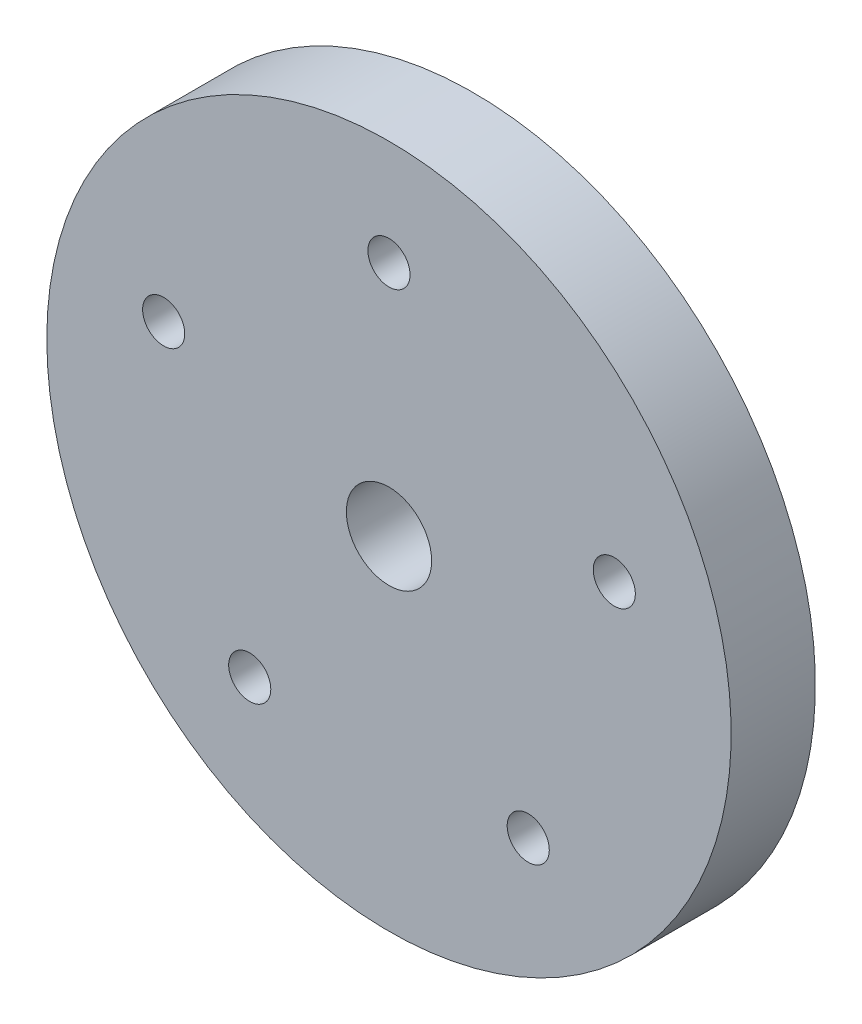
SolidWorks part; units mm, degrees
ref_plane "Ebene vorne" through (0, 0, 0) normal (0, 0, 1) x (1, 0, 0)
ref_plane "Ebene oben" through (0, 0, 0) normal (0, 1, 0) x (1, 0, 0)
ref_plane "Ebene rechts" through (0, 0, 0) normal (1, 0, 0) x (0, 0, -1)
sketch "Skizze1" plane through (0, 0, 0) normal (1, 0, 0) x (0, 0, -1)
  line L0 (0, 0) -> (0, -44862.1348) construction
  line L1 (0, 0) -> (-44862.1348, 0) construction
  line L2 (0, 0) -> (20, 0)
  line L3 (20, 0) -> (20, 15)
  line L4 (20, 15) -> (8, 15)
  line L5 (8, 15) -> (8, 32.5)
  line L6 (8, 32.5) -> (0, 32.5)
  line L7 (0, 32.5) -> (0, 0)
  dimension "D1" = 30
  dimension "D2" = 65
  dimension "D3" = 20
  dimension "D4" = 12
revolve "Rotation1" add sketch "Skizze1" angle 360 about L1
hole_wizard "Ø4.0 (4) Heat Insert M3" positions "Skizze2" profile "Skizze3" hole size "Ø4.0" standard "ISO" end condition through all
sketch "Skizze2" plane through (0, 0, 0) normal (0, 0, 1) x (1, 0, 0)
  circle A0 centre (0, 0) radius 22.5 construction
  point P7 (0, 22.5)
  dimension "D1" = 45
sketch "Skizze3" plane through (0, 22.5, 0) normal (1, 0, 0) x (0, -1, 0)
  line L0 (0, 0) -> (0, 20)
  line L1 (0, 20) -> (2, 20)
  line L2 (2, 20) -> (2, 0)
  line L5 (2, 0) -> (0, 0)
  line L11 (0, -6.35) -> (0, 107.95) construction
  dimension "Bohrerdurchmesser" = 4
  dimension "Bohrungstiefe" = 20
hole_wizard "Ø8.1 (8.1) Durchmesser Bohrung1" positions "Skizze4" profile "Skizze5" hole size "Ø8.1" standard "ISO" end condition through all
sketch "Skizze4" plane through (0, 0, 0) normal (0, 0, 1) x (1, 0, 0)
  point P0 (0, 0)
sketch "Skizze5" plane through (0, 0, 0) normal (1, 0, 0) x (0, -1, 0)
  line L0 (0, 0) -> (0, 20)
  line L1 (0, 20) -> (4.05, 20)
  line L2 (4.05, 20) -> (4.05, 0)
  line L5 (4.05, 0) -> (0, 0)
  line L11 (0, -6.35) -> (0, 107.95) construction
  dimension "Bohrerdurchmesser" = 8.1
  dimension "Bohrungstiefe" = 20
sketch "Skizze8" plane through (0, 0, -20) normal (0, 0, -1) x (-1, 0, 0)
  line L0 (0, 0) -> (0, 50000) construction
  circle A0 centre (0, 0) radius 10 construction
  circle A1 centre (0, 10) radius 2
  circle A2 centre (8.6603, -5) radius 2
  circle A3 centre (-8.6603, -5) radius 2
  point P14 (0, 0)
  dimension "D1" = 20
  dimension "D2" = 4
  dimension "D3" = 3
extrude "Schnitt-Linear austragen1" cut sketch "Skizze8" against normal blind 7
pattern_circular "Kreismuster1" count 5 over 360 about axis through (0, 0, 0) along (0, 0, -1) of "Ø4.0 (4) Heat Insert M3"
